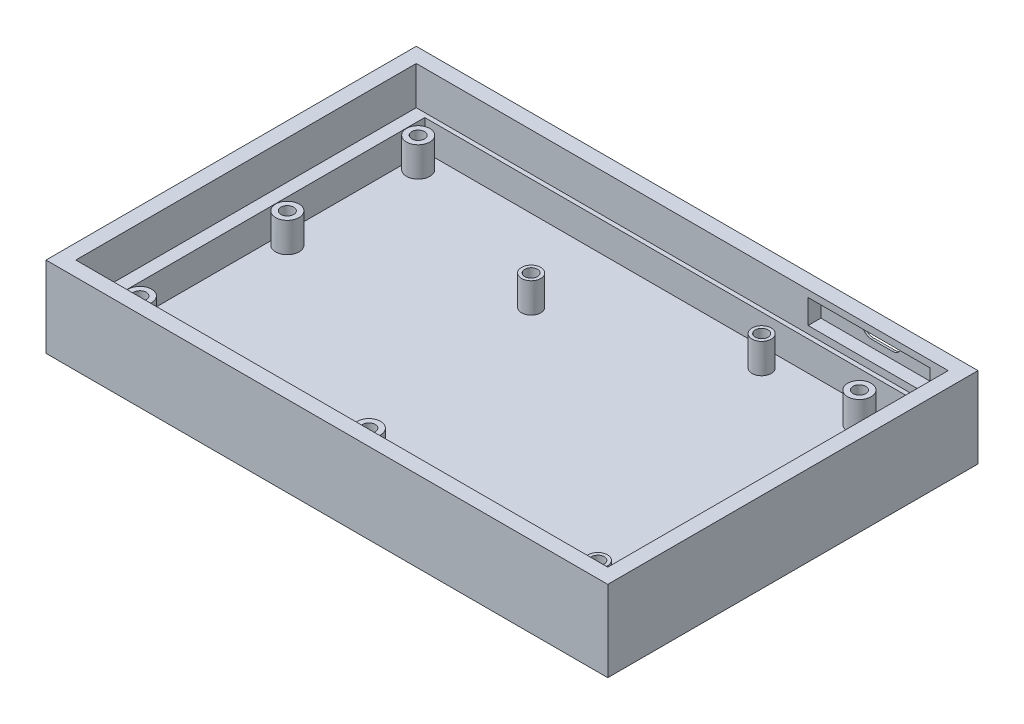
SolidWorks part; units mm, degrees
ref_plane "Front Plane" through (0, 0, 0) normal (0, 0, 1) x (1, 0, 0)
ref_plane "Top Plane" through (0, 0, 0) normal (0, 1, 0) x (1, 0, 0)
ref_plane "Right Plane" through (0, 0, 0) normal (1, 0, 0) x (0, 0, -1)
sketch "Sketch1" plane through (0, 0, 0) normal (0, 1, 0) x (1, 0, 0)
  line L0 (-66, 43.5) -> (66, 43.5)
  line L1 (-62.5, 40) -> (62.5, 40)
  line L2 (-62.5, 40) -> (-62.5, -40)
  line L3 (-62.5, -40) -> (62.5, -40)
  line L4 (62.5, 40) -> (62.5, -40)
  line L5 (-62.5, 40) -> (62.5, -40) construction
  line L6 (-62.5, -40) -> (62.5, 40) construction
  line L7 (66, 43.5) -> (66, -43.5)
  line L8 (-66, -43.5) -> (66, -43.5)
  line L9 (-66, 43.5) -> (-66, -43.5)
  point P0 (0, 0)
  dimension "D1" = 125
  dimension "D2" = 80
  dimension "D3" = 3.5
extrude "Boss-Extrude1" add sketch "Sketch1" along normal blind 3 contours L2 L1 L4 L3
extrude "Boss-Extrude2" add sketch "Sketch1<3>" along normal blind 19
sketch "Sketch1<3>" plane through (0, 0, 0) normal (0, 1, 0) x (1, 0, 0) same geometry as "Sketch1"
sketch "Sketch2" plane through (0, 0, 0) normal (0, 1, 0) x (1, 0, 0)
  line L1 (-62.5, -40) -> (62.5, -40)
  line L2 (-62.5, -40) -> (-62.5, 40)
  line L3 (-62.5, 40) -> (62.5, 40)
  line L4 (62.5, -40) -> (62.5, 40)
  line L9 (-59.5, 39) -> (60.5, 39)
  line L10 (-59.5, 39) -> (-59.5, -37)
  line L11 (-59.5, -37) -> (60.5, -37)
  line L12 (60.5, 39) -> (60.5, -37)
  point P0 (0, 0)
  point P9 (0, 0)
  dimension "D1" = 3
  dimension "D2" = 2
  dimension "D3" = 1
  dimension "D4" = 3
extrude "Boss-Extrude3" add sketch "Sketch2" along normal blind 10
sketch "Sketch3" plane through (0, 0, -40) normal (0, 0, -1) x (-1, 0, 0)
  line L1 (-58.2575, 17.4158) -> (-29.5791, 17.4158)
  line L2 (-58.2575, 17.4158) -> (-58.2575, 11.717)
  line L3 (-58.2575, 11.717) -> (-29.5791, 11.717)
  line L4 (-29.5791, 17.4158) -> (-29.5791, 11.717)
extrude "Cut-Extrude1" cut sketch "Sketch3" along normal blind 3
sketch "Sketch4" plane through (0, 0, -43.5) normal (0, 0, -1) x (-1, 0, 0)
  line L0 (-46.4548, 15.317) -> (-41.3575, 15.317) construction
  line L1 (-46.4548, 17.2566) -> (-41.3575, 17.2566)
  line L2 (-46.4548, 13.3774) -> (-41.3575, 13.3774)
  arc A0 (-46.4548, 17.2566) -> (-46.4548, 13.3774) centre (-46.4548, 15.317) ccw
  arc A1 (-41.3575, 13.3774) -> (-41.3575, 17.2566) centre (-41.3575, 15.317) ccw
  point P2 (-43.9062, 15.317)
extrude "Cut-Extrude2" cut sketch "Sketch4" against normal blind 3
sketch "Sketch5" plane through (0, 3, 0) normal (0, 1, 0) x (1, 0, 0)
  line L0 (-56.6664, -30.7729) -> (50.9406, -30.7729) construction
  line L1 (-56.6664, 34.6235) -> (-56.6664, -30.7729) construction
  circle A0 centre (-56.6664, -30.7729) radius 2.75
  circle A1 centre (-56.6664, 34.6235) radius 2.75
  circle A2 centre (-56.6664, 3.8749) radius 2.75
  circle A3 centre (-15.3764, 19.8794) radius 2.2593
  circle A4 centre (24.0416, 34.6235) radius 2.2593
  circle A5 centre (50.9406, -30.7729) radius 2.2593
  circle A6 centre (-2.8629, -30.7729) radius 2.75
  circle A7 centre (47.0168, 34.6235) radius 2.75
  circle A8 centre (-56.6664, 34.6235) radius 1.5
  circle A9 centre (-15.3764, 19.8794) radius 1.5
  circle A10 centre (24.0416, 34.6235) radius 1.5
  circle A11 centre (47.0168, 34.6235) radius 1.5
  circle A12 centre (-2.8629, -30.7729) radius 1.5
  circle A13 centre (50.9406, -30.7729) radius 1.5
  circle A14 centre (-56.6664, -30.7729) radius 1.5
  circle A15 centre (-56.6664, 3.8749) radius 1.5
  dimension "D1" = 5.5
  dimension "D2" = 3
extrude "Boss-Extrude4" add sketch "Sketch5" along normal blind 7
